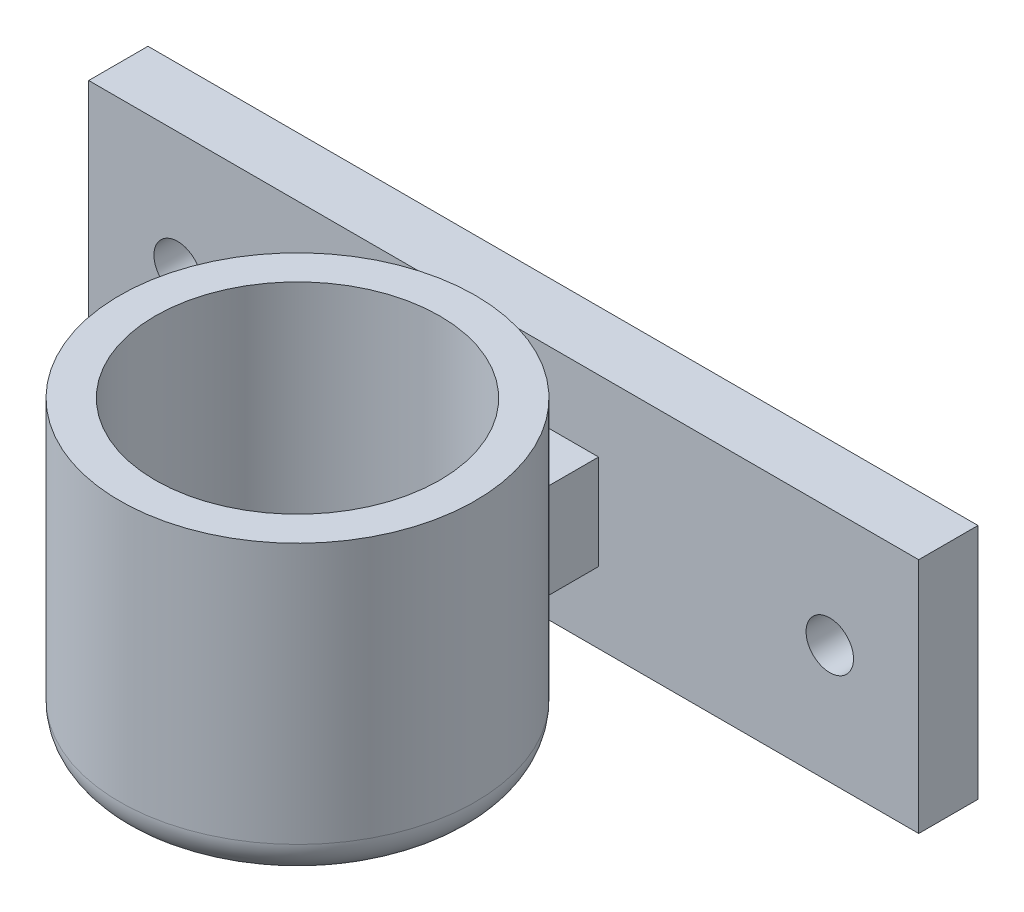
SolidWorks part; units mm, degrees
ref_plane "Front Plane" through (0, 0, 0) normal (0, 0, 1) x (1, 0, 0)
ref_plane "Top Plane" through (0, 0, 0) normal (0, 1, 0) x (1, 0, 0)
ref_plane "Right Plane" through (0, 0, 0) normal (1, 0, 0) x (0, 0, -1)
sketch "Sketch1" plane through (0, 0, 0) normal (0, 0, 1) x (1, 0, 0)
  line L0 (-29.3443, 30.6557) -> (40.6557, 30.6557)
  line L1 (40.6557, 30.6557) -> (40.6557, 10.6557)
  line L2 (40.6557, 10.6557) -> (-29.3443, 10.6557)
  line L3 (-29.3443, 30.6557) -> (-29.3443, 10.6557)
  circle A0 centre (-21.8443, 20.6557) radius 2
  circle A1 centre (33.1557, 20.6557) radius 2
  dimension "D3" = 4
  dimension "D4" = 4
  dimension "D1" = 70
  dimension "D2" = 20
  dimension "D5" = 10
  dimension "D6" = 10
  dimension "D7" = 55
  dimension "D8" = 7.5
extrude "Boss-Extrude1" add sketch "Sketch1" along normal mid plane 5
ref_plane "Plane2" through (0, 0, 3) normal (0, 0, 1) x (1, 0, 0)
sketch "Sketch4" plane through (0, 0, 2.5) normal (0, 0, 1) x (1, 0, 0)
  line L4 (5.6557, 24.6557) -> (13.6557, 24.6557)
  line L5 (-29.3443, 10.6557) -> (40.6557, 10.6557) construction
  line L10 (-29.3443, 30.6557) -> (-29.3443, 10.6557) construction
  line L11 (5.6557, 24.6557) -> (-2.3443, 24.6557)
  line L12 (-2.3443, 24.6557) -> (-2.3443, 16.6557)
  line L13 (-2.3443, 16.6557) -> (5.6557, 16.6557)
  line L14 (13.6557, 24.6557) -> (13.6557, 16.6557)
  line L15 (13.6557, 16.6557) -> (5.6557, 16.6557)
  point P0 (5.6557, 20.6557)
  point P1 (5.6557, 10.6557)
  point P4 (5.6557, 24.6557)
  point P7 (5.6557, 16.6557)
  point P8 (12.7739, 24.2235)
  point P9 (12.7739, 17.4691)
  point P10 (-1.0007, 17.4691)
  point P11 (-2.3443, 24.6557)
  point P15 (5.6557, 10.6557)
  point P18 (5.6557, 30.6557)
  dimension "D1" = 10
  dimension "D2" = 10
  dimension "D3" = 35
  dimension "D4" = 8
  dimension "D5" = 4
  dimension "D6" = 4
  dimension "D7" = 8
extrude "Boss-Extrude2" add sketch "Sketch4" along normal blind 5
ref_plane "Plane3" through (0, 16.6557, 0) normal (0, -1, 0) x (-1, 0, 0)
sketch "Sketch6" plane through (0, 16.6557, 0) normal (0, -1, 0) x (-1, 0, 0)
  line L0 (2.3443, -2.5) -> (-13.6557, -2.5) construction
  circle A0 centre (-5.6557, -19.8886) radius 12
  circle A1 centre (-5.6557, -19.8886) radius 15
  point P2 (-5.6557, -2.5)
  dimension "D1" = 24
  dimension "D2" = 30
extrude "Boss-Extrude3" add sketch "Sketch6" against normal blind 17 and the other way blind 5
sketch "Sketch7" plane through (0, 16.6557, 0) normal (0, -1, 0) x (1, 0, 0)
  circle A0 centre (5.6557, 19.8886) radius 14
  circle A1 centre (5.6557, 19.8886) radius 1.975
  dimension "D1" = 3.95
sketch "Sketch9" plane through (0, 16.6557, 0) normal (0, -1, 0) x (-1, 0, 0)
  line L0 (29.3443, 2.5) -> (-40.6557, 2.5) construction
  line L1 (29.3443, -2.5) -> (-40.6557, -2.5) construction
  point P0 (-5.6557, 2.5)
  point P1 (-5.6557, -2.5)
  point P4 (8.0065, -2.5)
  point P7 (-20.0906, -2.5)
  point P8 (-5.6557, -5.3905)
sketch "Sketch10" plane through (0, 11.6557, 0) normal (0, -1, 0) x (1, 0, 0)
  circle A0 centre (5.6557, 19.8886) radius 15
  dimension "D1" = 30
extrude "Boss-Extrude4" add sketch "Sketch10" along normal blind 3
sketch "Sketch11" plane through (0, 8.6557, 0) normal (0, -1, 0) x (1, 0, 0)
  circle A0 centre (5.6557, 19.8886) radius 2.5
  dimension "D1" = 5
extrude "Cut-Extrude1" cut sketch "Sketch11" against normal blind 3
fillet "Fillet1" radius 3 1 edges at (5.6557, 8.6557, 4.8886)
